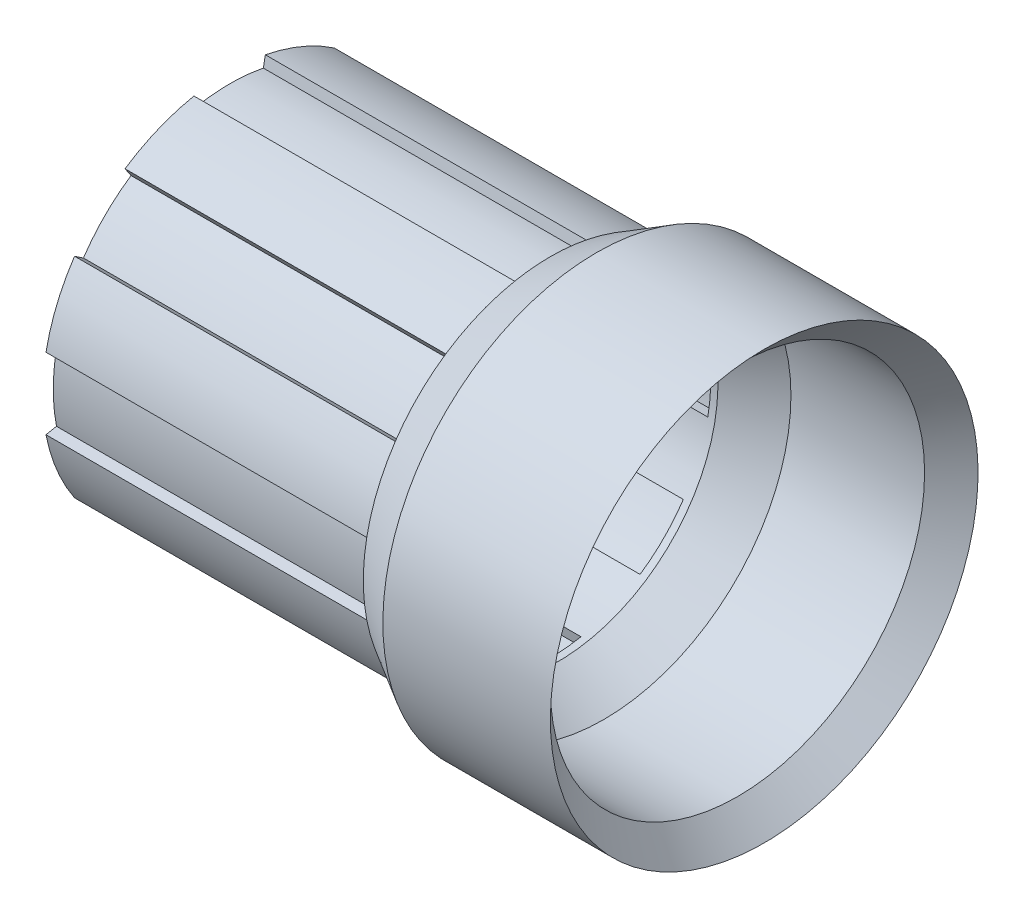
SolidWorks part; units mm, degrees
ref_plane "Front" through (0, 0, 0) normal (0, 0, 1) x (1, 0, 0)
ref_plane "Top" through (0, 0, 0) normal (0, 1, 0) x (1, 0, 0)
ref_plane "Right" through (0, 0, 0) normal (1, 0, 0) x (0, 0, -1)
sketch "Sketch2" plane through (0, 0, 0) normal (0, 0, 1) x (1, 0, 0)
  line L0 (0, -1000) -> (0, 0) construction
  line L1 (1000, 0) -> (0, 0) construction
  line L2 (-10, 3) -> (-10, 3.5)
  line L4 (0, 3.5) -> (0, 4)
  line L5 (-10, 3.5) -> (-4, 3.5)
  line L6 (-4, 3.5) -> (-3.134, 4)
  line L7 (-10, 3) -> (-3.866, 3)
  line L8 (-3.134, 4) -> (0, 4)
  line L9 (-3.866, 3) -> (-3, 3.5)
  line L10 (-3, 3.5) -> (0, 3.5)
  line L11 (0, 3.5) -> (0, 50000) construction
  line L12 (-10, 0) -> (-50000, 0) construction
  dimension "D1" = 8
  dimension "D2" = 7
  dimension "D3" = 30
  dimension "D4" = 10
  dimension "D5" = 6
  dimension "D6" = 6
revolve "Revolve1" add sketch "Sketch2" angle 360 about L12
sketch "Sketch3" plane through (-10, 0, 0) normal (-1, 0, 0) x (0, 0, 1)
  line L0 (0, 0) -> (50000, 0) construction
  line L1 (0, 0) -> (0, 50000) construction
  line L2 (0.5724, 2.9449) -> (0.6106, 3.1412)
  line L3 (-0.5724, 2.9449) -> (-0.6106, 3.1412)
  line L6 (0.6678, 3.4357) -> (9511.6634, 48933.2663) construction
  line L7 (0, 0) -> (0.6678, 3.4357) construction
  line L8 (0, 0) -> (-0.6678, 3.4357) construction
  line L9 (-0.6297, 3.2394) -> (-0.6678, 3.4357)
  line L10 (0.6297, 3.2394) -> (0.6678, 3.4357)
  line L11 (-0.6678, 3.4357) -> (-9511.6634, 48933.2663) construction
  circle A1 centre (0, 0) radius 3 construction
  circle A2 centre (0, 0) radius 3.5 construction
  arc A4 (0.6678, 3.4357) -> (-0.6678, 3.4357) centre (0, 0) ccw
  arc A5 (0.6106, 3.1412) -> (-0.6106, 3.1412) centre (0, 0) ccw
  arc A6 (0.5724, 2.9449) -> (-0.5724, 2.9449) centre (0, 0) ccw
  arc A7 (0.6297, 3.2394) -> (-0.6297, 3.2394) centre (0, 0) ccw
  dimension "D1" = 3.2
  dimension "D2" = 3.3
  dimension "D3" = 22
extrude "Cut-Extrude1" cut sketch "Sketch3" against normal blind 6
pattern_circular "CirPattern1" count 8 over 360 about axis through (-10, 0, 0) along (1, 0, 0) of "Cut-Extrude1"
chamfer "Chamfer1" distance 0.5 angle 45 1 edges at (0, 3.5, 0)
